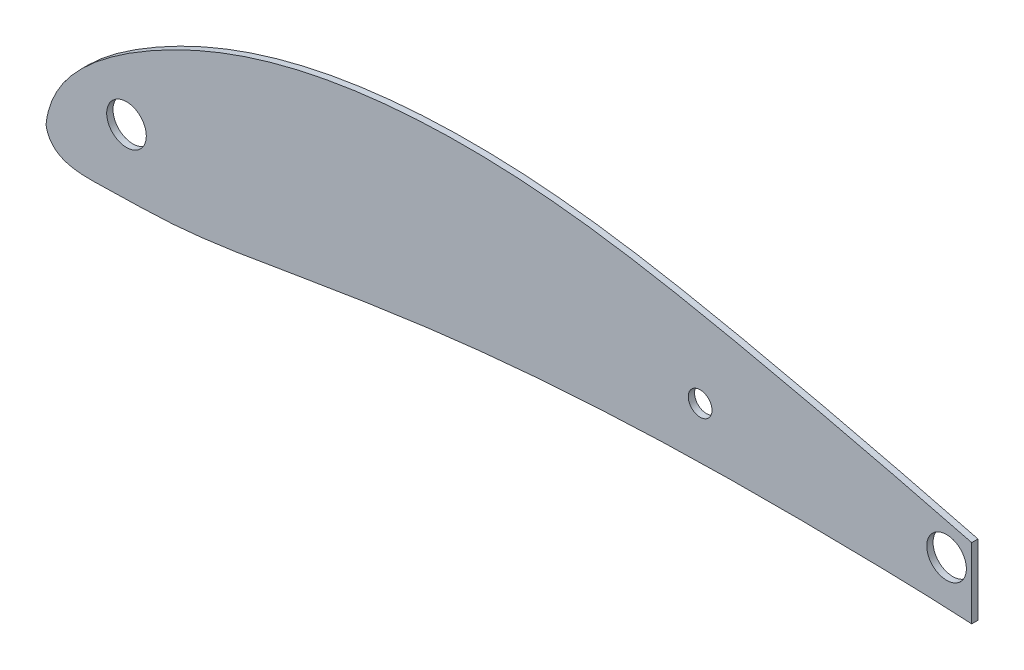
SolidWorks part; units mm, degrees
material "Balsa"
ref_plane "Front Plane" through (0, 0, 0) normal (0, 0, 1) x (1, 0, 0)
ref_plane "Top Plane" through (0, 0, 0) normal (0, 1, 0) x (1, 0, 0)
ref_plane "Right Plane" through (0, 0, 0) normal (1, 0, 0) x (0, 0, -1)
sketch "Sketch1" plane through (0, 0, 0) normal (0, 0, 1) x (1, 0, 0)
  spline S0 degree 3 poles (0.0006, 0.0001) (0.8106, 7.3592) (8.6491, 17.8566) (26.2867, 29.9752) (52.1111, 42.0692) (89.5976, 49.2908) (131.4008, 47.8848) (173.2567, 40.0411) (217.9611, 29.613) (256.9521, 19.5289) (290.3598, 8.711) (301.2732, 4.3828) (314.8169, -0.5162) (309.8463, 0.0001) knots 0 0 0 0 0.060864 0.113688 0.188609 0.312909 0.448482 0.557612 0.691544 0.852438 0.929756 0.976058 1 1 1 1
  spline S1 degree 3 poles (309.8463, 0.0001) (303.9568, 1.471) (293.9895, 2.094) (276.264, 4.5144) (260.8463, 5.4274) (235.8588, 7.8703) (205.1014, 8.8381) (157.7186, 9.0307) (110.4973, 6.1815) (66.5062, -0.5867) (36.4547, -6.0985) (15.3166, -6.1891) (1.2307, -6.9241) (0.0006, 0.0001) knots 0 0 0 0 0.057787 0.095275 0.171021 0.205339 0.335319 0.464904 0.658702 0.785512 0.893517 0.943092 1 1 1 1
extrude "Boss-Extrude1" add sketch "Sketch1" along normal blind 1.5875
sketch "Sketch2" plane through (0, 0, 1.5875) normal (0, 0, 1) x (1, 0, 0)
  circle A0 centre (20.32, 10.16) radius 5
  circle A1 centre (227.2963, 19.0501) radius 5
  dimension "D2" = 10
  dimension "D3" = 10
  dimension "D6" = 20.32
  dimension "D1" = 82.55
  dimension "D4" = 19.05
  dimension "D5" = 10.16
extrude "Cut-Extrude1" cut sketch "Sketch2" against normal through all
sketch "Sketch3" plane through (0, 0, 1.5875) normal (0, 0, 1) x (1, 0, 0)
  line L1 (350.4863, -6.3499) -> (233.6463, -6.3499)
  line L2 (350.4863, -6.3499) -> (350.4863, 44.4501)
  line L3 (350.4863, 44.4501) -> (233.6463, 44.4501)
  line L4 (233.6463, -6.3499) -> (233.6463, 44.4501)
  circle A0 centre (227.2963, 19.0501) radius 5 construction
  dimension "D1" = 6.35
  dimension "D2" = 116.84
  dimension "D3" = 50.8
  dimension "D4" = 44.45
extrude "Cut-Extrude2" cut sketch "Sketch3" against normal through all contours L3 L4 L1 L2
sketch "Sketch4" plane through (0, 0, 0) normal (0, 0, -1) x (-1, 0, 0)
  circle A0 centre (-165.1006, 21.5901) radius 3
  dimension "D1" = 6
  dimension "D2" = 165.1
  dimension "D3" = 21.59
extrude "Cut-Extrude3" cut sketch "Sketch4" against normal blind 2.54
